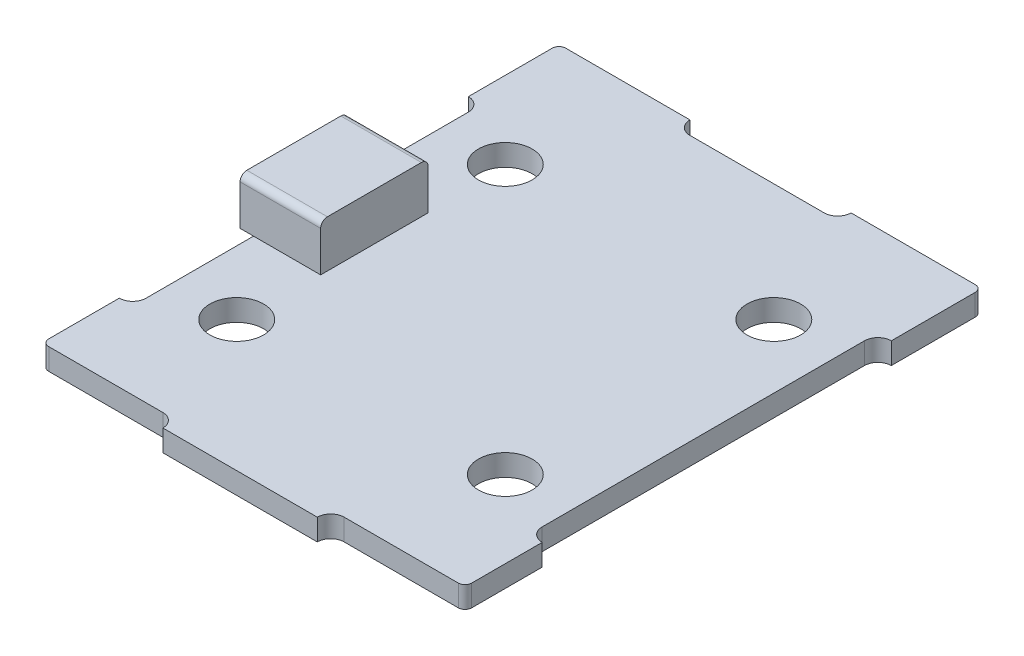
SolidWorks part; units mm, degrees
ref_plane "Front Plane" through (0, 0, 0) normal (0, 0, 1) x (1, 0, 0)
ref_plane "Top Plane" through (0, 0, 0) normal (0, 1, 0) x (1, 0, 0)
ref_plane "Right Plane" through (0, 0, 0) normal (1, 0, 0) x (0, 0, -1)
sketch "Sketch1" plane through (0, 0, 0) normal (0, 1, 0) x (1, 0, 0)
  line L0 (-15.75, 0) -> (15.75, 0) construction
  line L1 (15.75, 19.75) -> (-15.75, 19.75)
  line L2 (15.75, 19.75) -> (15.75, -19.75)
  line L3 (15.75, -19.75) -> (-15.75, -19.75)
  line L4 (-15.75, 19.75) -> (-15.75, -19.75)
  line L5 (15.75, 19.75) -> (-15.75, -19.75) construction
  line L6 (15.75, -19.75) -> (-15.75, 19.75) construction
  line L7 (0, 19.75) -> (0, -19.75) construction
  line L8 (-14.75, -13) -> (-15.75, -13)
  line L9 (-14.75, -13) -> (-14.75, 13)
  line L10 (-14.75, 13) -> (-15.75, 13)
  line L11 (-15.75, -13) -> (-15.75, 13)
  line L12 (-14.75, -13) -> (-15.75, 13) construction
  line L13 (-14.75, 13) -> (-15.75, -13) construction
  line L14 (14.75, -13) -> (15.75, -13)
  line L15 (15.75, -13) -> (15.75, 13)
  line L16 (14.75, 13) -> (15.75, 13)
  line L17 (14.75, -13) -> (14.75, 13)
  line L18 (15.75, -19.75) -> (5.75, -19.75)
  line L19 (10, -10) -> (-10, -10)
  line L20 (10, -10) -> (10, 10)
  line L21 (10, 10) -> (-10, 10)
  line L22 (-10, -10) -> (-10, 10)
  line L23 (10, -10) -> (-10, 10) construction
  line L24 (10, 10) -> (-10, -10) construction
  line L25 (-6, 19.75) -> (6, 19.75)
  line L26 (-6, 19.75) -> (-6, 18.75)
  line L27 (-6, 18.75) -> (6, 18.75)
  line L28 (6, 19.75) -> (6, 18.75)
  line L29 (-6, 19.75) -> (6, 18.75) construction
  line L30 (-6, 18.75) -> (6, 19.75) construction
  line L31 (-15.75, -19.75) -> (-5.75, -19.75)
  line L32 (-15.75, -19.75) -> (-15.75, -18.75)
  line L33 (-15.75, -18.75) -> (-5.75, -18.75)
  line L34 (-5.75, -19.75) -> (-5.75, -18.75)
  line L35 (5.75, -19.75) -> (5.75, -18.75)
  line L36 (15.75, -18.75) -> (5.75, -18.75)
  line L37 (15.75, -19.75) -> (15.75, -18.75)
  circle A0 centre (-10, 10) radius 2
  circle A1 centre (10, 10) radius 2
  circle A2 centre (10, -10) radius 2
  circle A3 centre (-10, -10) radius 2
  point P0 (0, 0)
  point P8 (-15.25, 0)
  point P21 (0, 0)
  point P28 (0, 19.25)
  dimension "D5" = 4
  dimension "D1" = 39.5
  dimension "D2" = 31.5
  dimension "D3" = 1
  dimension "D4" = 26
  dimension "D6" = 20
  dimension "D7" = 12
  dimension "D8" = 10
extrude "Boss-Extrude1" add sketch "Sketch1" along normal blind 1.6 contours L14 L17 L16 L2 L1 L4 L10 L9 L8 L3 A3 L22 A0 L21 A1 L20 A2 L19 | A3 L19 A2 L20 A1 L21 A0 L22 region at (15.2448, 0, -16.375) region at (0, 0, 0)
sketch "Sketch2" plane through (0, 1.6, 0) normal (0, 1, 0) x (1, 0, 0)
  line L0 (-14.75, 0) -> (14.75, 0) construction
  line L1 (-14.75, -13) -> (-14.75, 13) construction
  line L2 (14.75, -13) -> (14.75, 13) construction
  line L4 (-15.75, 4) -> (-9.75, 4)
  line L5 (-15.75, 4) -> (-15.75, -4)
  line L6 (-15.75, -4) -> (-9.75, -4)
  line L7 (-9.75, 4) -> (-9.75, -4)
  line L8 (-15.75, 4) -> (-9.75, -4) construction
  line L9 (-15.75, -4) -> (-9.75, 4) construction
  line L11 (-15.75, 19.75) -> (-15.75, 13) construction
  point P6 (-12.75, 0)
  dimension "D1" = 8
  dimension "D2" = 6
extrude "Boss-Extrude2" add sketch "Sketch2" along normal blind 3.5
fillet "Fillet1" radius 1 8 edges at (14.75, 0.8, -13) (14.75, 0.8, 13) (-6, 0.8, -18.75) (6, 0.8, -18.75) (-14.75, 0.8, -13) (-14.75, 0.8, 13) (-5.75, 0.8, 18.75) (5.75, 0.8, 18.75)
fillet "Fillet2" radius 0.5 6 edges at (-15.75, 0.8, -19.75) (15.75, 0.8, -19.75) (15.75, 0.8, 18.75) (-15.75, 0.8, 18.75) (-12.75, 5.1, -4) (-12.75, 5.1, 4)
sketch "Sketch3" plane through (-15.75, 0, 0) normal (-1, 0, 0) x (0, 0, 1)
  line L8 (3.5, 4.6) -> (-3.5, 4.6)
  line L9 (-3.5, 4.6) -> (-3.5, 2.1)
  line L10 (-3.5, 2.1) -> (3.5, 2.1)
  line L11 (3.5, 2.1) -> (3.5, 4.6)
  line L12 (3.5, 4.6) -> (-3.5, 4.6)
  line L13 (-3.5, 4.6) -> (-3.5, 2.1)
  line L14 (-3.5, 2.1) -> (3.5, 2.1)
  line L15 (3.5, 2.1) -> (3.5, 4.6)
  dimension "D1" = 0.5
extrude "Cut-Extrude1" cut sketch "Sketch3" against normal blind 5
